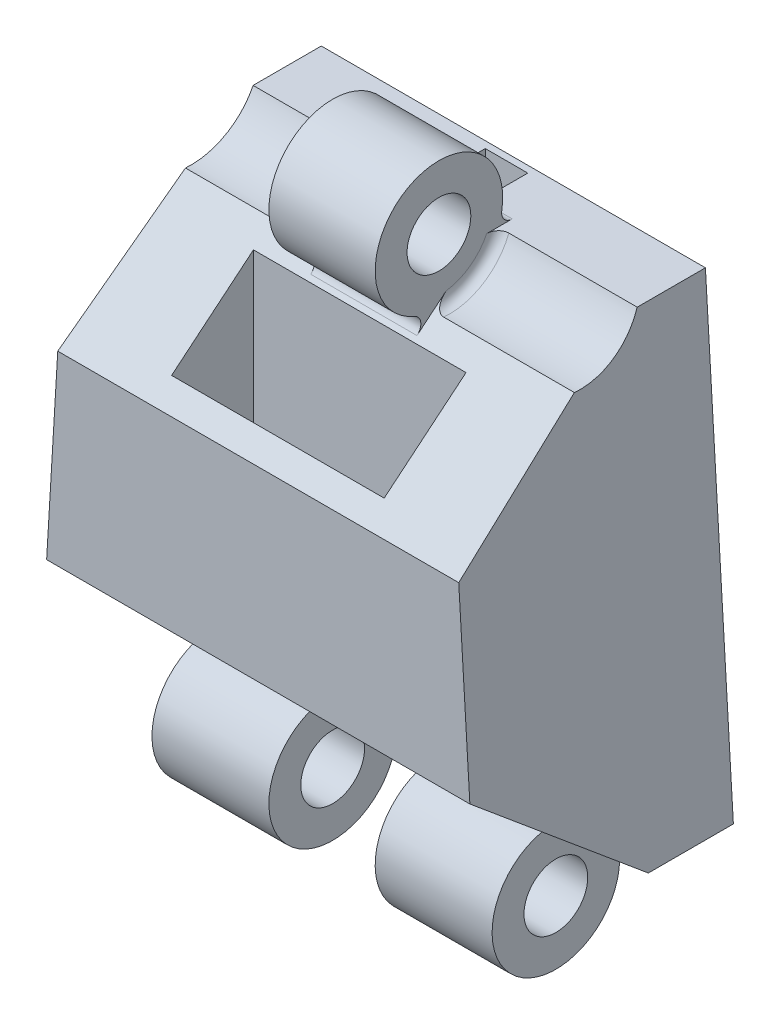
SolidWorks part; units mm, degrees
ref_plane "Front Plane" through (0, 0, 0) normal (0, 0, 1) x (1, 0, 0)
ref_plane "Top Plane" through (0, 0, 0) normal (0, 1, 0) x (1, 0, 0)
ref_plane "Right Plane" through (0, 0, 0) normal (1, 0, 0) x (0, 0, -1)
sketch "Sketch1" plane through (0, 0, 0) normal (0, 0, 1) x (1, 0, 0)
  line L0 (-56.5743, 0) -> (-35.8731, 0)
  line L1 (-55.2587, 22) -> (-37.1887, 22)
  line L2 (-56.5743, 0) -> (-55.2587, 22)
  line L3 (-35.8731, 0) -> (-37.1887, 22)
extrude "Boss-Extrude1" add sketch "Sketch1" along normal blind 12
sketch "Sketch2" plane through (0, 0, 12) normal (0, 0, 1) x (1, 0, 0)
  line L0 (-35.8731, 0) -> (-56.5743, 0)
  line L1 (-46.2237, 0) -> (-46.2237, 29.5391)
ref_plane "Plane1" through (-46.2237, 0, 0) normal (1, 0, 0) x (0, 0, -1)
sketch "Sketch3" plane through (-46.2237, 0, 0) normal (1, 0, 0) x (0, 0, -1)
  line L0 (0, 0) -> (-4, 0)
  line L1 (-12, 0) -> (0, 0) construction
  line L2 (-4, 0) -> (-12, 6.614)
  line L3 (-12, 0) -> (-12, 22) construction
  line L4 (-12, 6.614) -> (-12, 0)
  line L5 (-12, 0) -> (-4, 0)
extrude "Cut-Extrude1" cut sketch "Sketch3" against normal through all both and the other way through all contours L4 L5 L2 region at (-46.2237, 2.2047, 9.3333)
sketch "Sketch6" plane through (-46.2237, 0, 0) normal (1, 0, 0) x (0, 0, -1)
  line L1 (0, 0) -> (-12, 0)
  line L2 (-6, 0) -> (-6, -1.1)
  circle A0 centre (-6, -1.1) radius 1.5
  circle A1 centre (-6, -1.1) radius 3
extrude "Boss-Extrude2" add sketch "Sketch6" along normal mid plane 16 contours L1 A1 A0 | L1 A1 A0 region at (-46.2237, -0.5537, 3.1241) region at (-46.2237, 0.8343, 6)
extrude "Cut-Extrude2" cut sketch "Sketch6<3>" against normal mid plane 5 contours L1 A1 A0 | L1 A1 A0 region at (-46.2237, -0.5537, 3.1241) region at (-46.2237, 0.8343, 6)
sketch "Sketch6<3>" plane through (-46.2237, 0, 0) normal (1, 0, 0) x (0, 0, -1) same geometry as "Sketch6"
sketch "Sketch8" plane through (-46.2237, 0, 0) normal (1, 0, 0) x (0, 0, -1)
  line L0 (0, 22) -> (-4, 22)
  line L1 (-12, 22) -> (0, 22) construction
  line L2 (-4, 22) -> (-12, 15.3704)
  line L3 (-12, 6.614) -> (-12, 22) construction
  line L4 (-12, 15.3704) -> (-12, 22)
  line L5 (-12, 22) -> (-4, 22)
extrude "Cut-Extrude3" cut sketch "Sketch8" against normal through all both and the other way through all contours L5 L4 L2 region at (-46.2237, 19.7901, 9.3333)
sketch "Sketch9" plane through (-46.2237, 0, 0) normal (1, 0, 0) x (0, 0, -1)
  line L0 (-12, 15.3704) -> (-12, 26.5168)
  line L1 (0, 22) -> (-12, 22)
  line L2 (-6, 22) -> (-6, 23.1)
  circle A0 centre (-6, 23.1) radius 1.5
  circle A1 centre (-6, 23.1) radius 3
extrude "Boss-Extrude3" add sketch "Sketch9" along normal mid plane 5 contours L1 A1 A0 | L1 A1 A0 region at (-46.2237, 21.1657, 6) region at (-46.2237, 22.0727, 4.0946)
sketch "Sketch11" plane through (-43.7237, 0, 0) normal (1, 0, 0) x (0, 0, -1)
  circle A0 centre (-6, 23.1) radius 3
extrude "Cut-Extrude4" cut sketch "Sketch11" along normal blind 10
sketch "Sketch12" plane through (-48.7237, 0, 0) normal (-1, 0, 0) x (0, 0, 1)
  circle A0 centre (6, 23.1) radius 3
extrude "Cut-Extrude5" cut sketch "Sketch12" along normal blind 10
fillet "Fillet1" radius 0.5 2 edges at (-46.2237, 22, 3.2089) (-46.2237, 20.1128, 6.2772)
fillet "Fillet2" radius 0.5 2 edges at (-48.7237, 20.5446, 4.4283) (-43.7237, 20.5446, 4.4283)
sketch "Sketch13" plane through (0, 15.008, 12.4372) normal (0, 0.77, 0.6381) x (1, 0, 0)
  line L0 (-46.2237, 0.5678) -> (-46.2237, 1.7678)
  line L1 (-55.6551, 0.5678) -> (-36.7922, 0.5678) construction
  line L2 (-46.2237, 1.7678) -> (-41.2237, 1.7678)
  line L3 (-41.2237, 1.7678) -> (-41.2237, 6.7678)
  line L4 (-41.2237, 6.7678) -> (-51.2237, 6.7678)
  line L5 (-51.2237, 6.7678) -> (-51.2237, 1.7678)
  line L6 (-51.2237, 1.7678) -> (-46.2237, 1.7678)
ref_plane "Plane2" through (0, 10, 0) normal (0, 1, 0) x (1, 0, 0)
sketch "Sketch14" plane through (0, 10, 0) normal (0, 1, 0) x (1, 0, 0)
  line L0 (-51.2237, -7.2262) -> (-51.2237, -11.076)
  line L1 (-51.2237, -11.076) -> (-41.2237, -11.076)
  line L2 (-41.2237, -11.076) -> (-41.2237, -7.2262)
  line L3 (-41.2237, -7.2262) -> (-51.2237, -7.2262)
extrude "Cut-Extrude6" cut sketch "Sketch14" against normal up to surface and the other way up to surface up to face at (-46.2237, 2.0775, 6.5128) other way up to face at (-46.2124, 19.1095, 7.4879)
sketch "Sketch15" plane through (-46.2237, 0, 0) normal (1, 0, 0) x (0, 0, -1)
  line L0 (0, 22) -> (-2.32, 22)
  line L1 (-3.2089, 22) -> (0, 22) construction
  line L2 (-2.32, 22) -> (-2.32, -2.974)
  line L3 (-2.32, -2.974) -> (-0.32, -2.974)
  line L4 (-0.32, -2.974) -> (-0.32, 23.0399)
extrude "Cut-Extrude7" cut sketch "Sketch15" against normal mid plane 2 contours L3 L4 L0 L2 region at (-46.2237, 9.513, 1.32)
